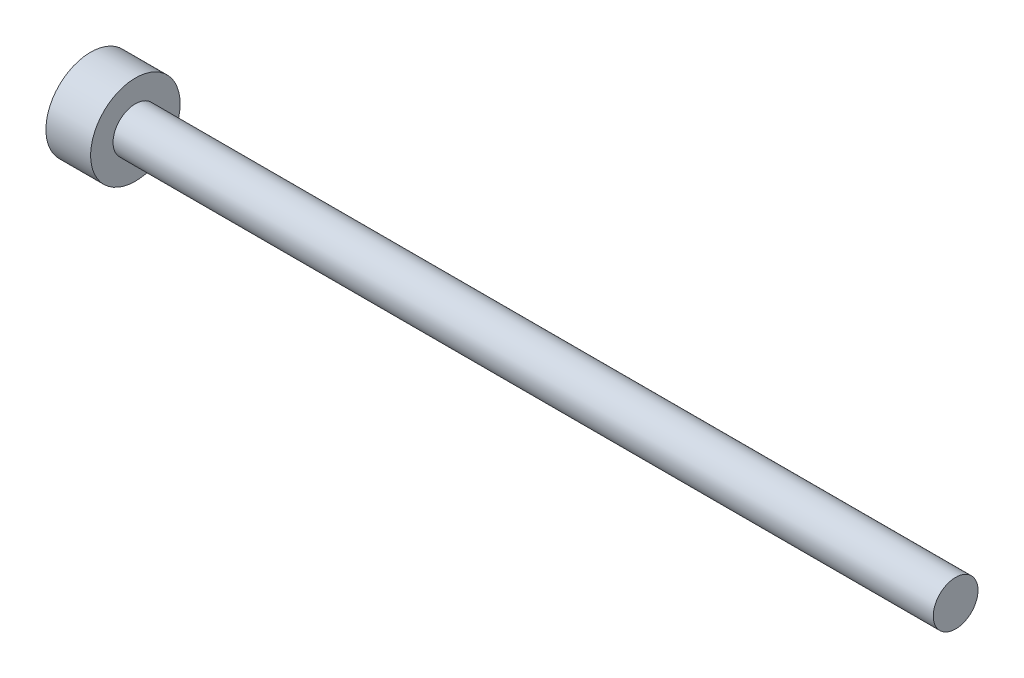
SolidWorks part; units mm, degrees
material "AISI 1045 Steel, cold drawn"
ref_plane "前视基准面" through (0, 0, 0) normal (0, 0, 1) x (1, 0, 0)
ref_plane "上视基准面" through (0, 0, 0) normal (0, 1, 0) x (1, 0, 0)
ref_plane "右视基准面" through (0, 0, 0) normal (1, 0, 0) x (0, 0, -1)
sketch "Sketch1" plane through (0, 0, 0) normal (1, 0, 0) x (0, 0, -1)
  circle A0 centre (0, 0) radius 3
  dimension "D1" = 6
extrude "Boss-Extrude1" add sketch "Sketch1" along normal blind 3
sketch "Sketch2" plane through (3, 0, 0) normal (1, 0, 0) x (0, 0, -1)
  circle A0 centre (0, 0) radius 1.5
  dimension "D1" = 3
extrude "Boss-Extrude2" add sketch "Sketch2" along normal blind 55
